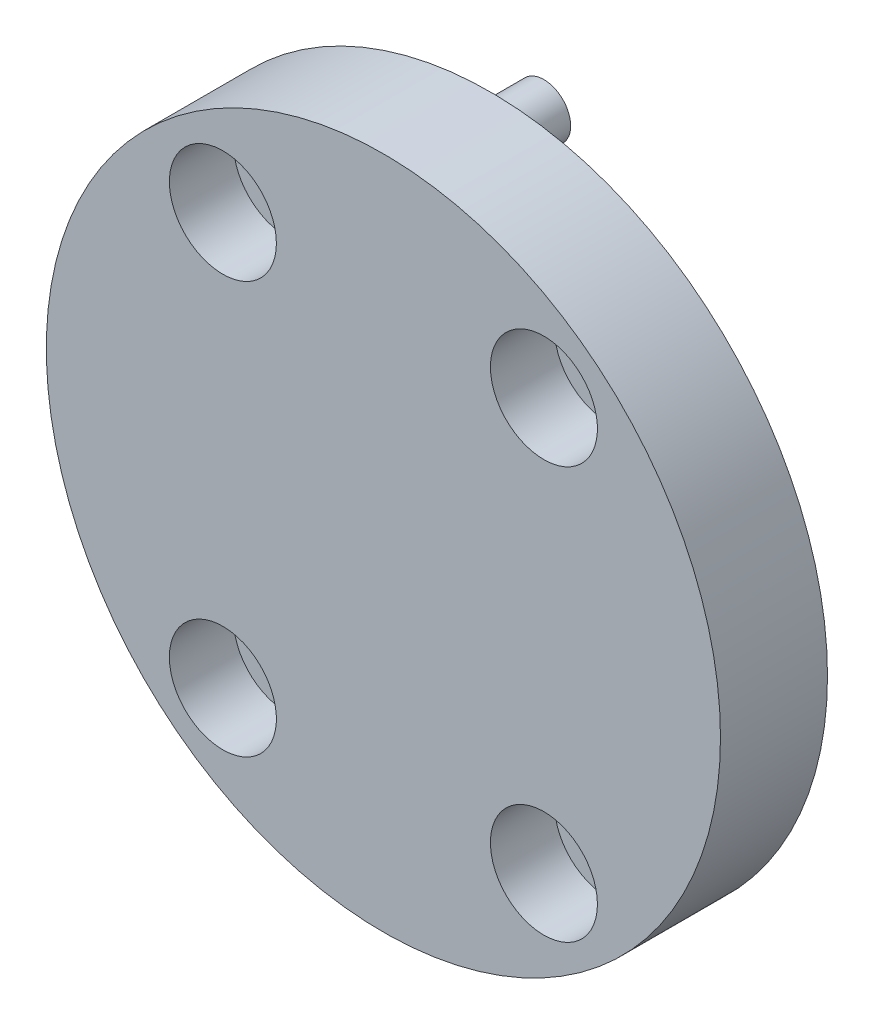
SolidWorks part; units mm, degrees
ref_plane "Front Plane" through (0, 0, 0) normal (0, 0, 1) x (1, 0, 0)
ref_plane "Top Plane" through (0, 0, 0) normal (0, 1, 0) x (1, 0, 0)
ref_plane "Right Plane" through (0, 0, 0) normal (1, 0, 0) x (0, 0, -1)
sketch "Sketch1" plane through (0, 0, 0) normal (0, 0, 1) x (1, 0, 0)
  line L0 (0, 68.837) -> (0, -56.2565) construction
  line L1 (0, 0) -> (49.701, 49.701) construction
  circle A0 centre (0, 0) radius 31.5
  dimension "D1" = 63
  dimension "D2" = 45
extrude "Boss-Extrude1" add sketch "Sketch1" along normal mid plane 10 contours A0
sketch "Sketch2" plane through (0, 0, 5) normal (0, 0, 1) x (1, 0, 0)
  line L0 (0, 0) -> (0, 31.5) construction
  line L1 (0, 0) -> (-31.5, 0) construction
  line L2 (0, 0) -> (-28.4203, 28.4203) construction
  circle A1 centre (0, 27.5) radius 2.5
  circle A3 centre (0, 0) radius 25
  circle A4 centre (-15, 19.2426) radius 3
  circle A5 centre (0, 0) radius 31.5 construction
  circle A6 centre (-15, -19.2426) radius 3
  circle A7 centre (15, -19.2426) radius 3
  circle A8 centre (15, 19.2426) radius 3
  circle A9 centre (-15, 19.2426) radius 5
  circle A10 centre (-15, -19.2426) radius 5
  circle A11 centre (15, -19.2426) radius 5
  circle A12 centre (15, 19.2426) radius 5
  dimension "D1" = 50
  dimension "D2" = 5
  dimension "D3" = 6
  dimension "D5" = 30
  dimension "D6" = 10
  dimension "D4" = 45
extrude "Cut-Extrude1" cut sketch "Sketch2" against normal through all contours A8 | A4 | A6 | A7
extrude "Boss-Extrude2" add sketch "Sketch2<4>" against normal blind 15 contours A1
sketch "Sketch2<4>" plane through (0, 0, 5) normal (0, 0, 1) x (1, 0, 0) same geometry as "Sketch2"
extrude "Cut-Extrude2" cut sketch "Sketch2<5>" against normal blind 6 contours A9 | A12 | A10 | A11
sketch "Sketch2<5>" plane through (0, 0, 5) normal (0, 0, 1) x (1, 0, 0) same geometry as "Sketch2"
